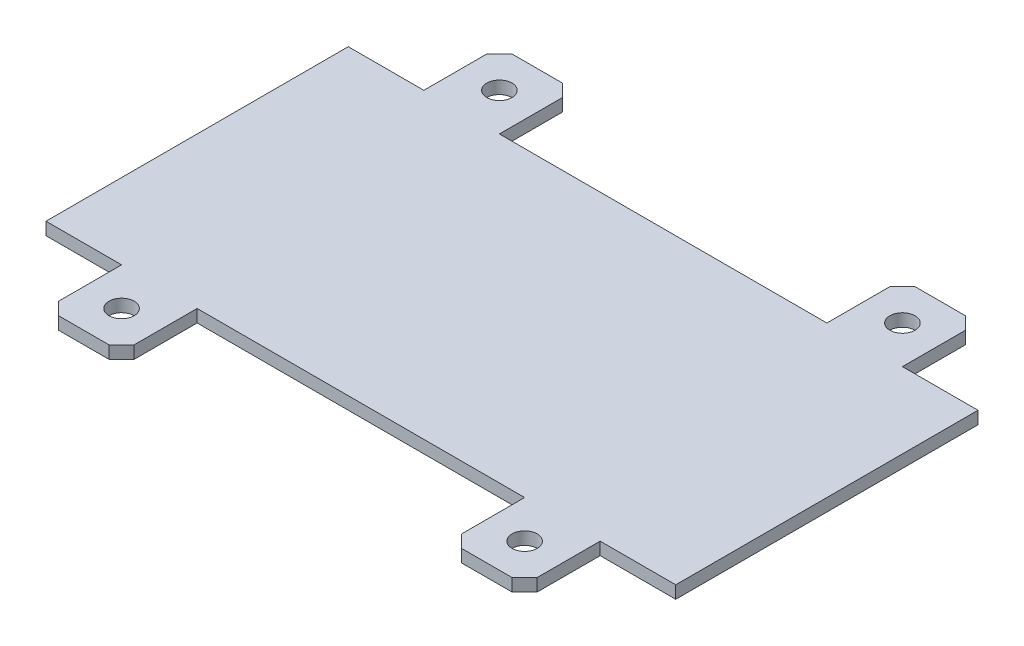
SolidWorks part; units mm, degrees
material "Сталь 3 ГОСТ 535-88"
ref_plane "Спереди" through (0, 0, 0) normal (0, 0, 1) x (1, 0, 0)
ref_plane "Сверху" through (0, 0, 0) normal (0, 1, 0) x (1, 0, 0)
ref_plane "Справа" through (0, 0, 0) normal (1, 0, 0) x (0, 0, -1)
sketch "Эскиз1" plane through (0, 0, 0) normal (0, 1, 0) x (1, 0, 0)
  line L1 (-125, 60) -> (125, 60)
  line L2 (-125, 60) -> (-125, -60)
  line L3 (-125, -60) -> (125, -60)
  line L4 (125, 60) -> (125, -60)
  line L5 (0, -60) -> (0, 60) construction
  line L6 (-125, 0) -> (125, 0) construction
  point P0 (0, 0)
  dimension "D1" = 120
  dimension "D2" = 250
extrude "Бобышка-Вытянуть1" add sketch "Эскиз1" along normal blind 5
sketch "Эскиз2" plane through (0, 0, 0) normal (0, 1, 0) x (1, 0, 0)
  line L0 (125, 60) -> (-125, 60) construction
  line L1 (-95, 60) -> (-65, 60)
  line L2 (-95, 60) -> (-95, 90)
  line L3 (-95, 90) -> (-65, 90)
  line L4 (-65, 60) -> (-65, 90)
  line L5 (-125, 60) -> (-125, -60) construction
  line L6 (-80, 90) -> (-80, 60) construction
  circle A0 centre (-80, 75) radius 5
  dimension "D4" = 10
  dimension "D1" = 30
  dimension "D2" = 30
  dimension "D3" = 30
extrude "Бобышка-Вытянуть2" add sketch "Эскиз2" along normal up to surface (5 mm away) separate body up to face at (0, 5, 0)
chamfer "Фаска1" distance 5 angle 45 2 edges at (-65, 2.5, -90) (-95, 2.5, -90)
mirror "Зеркальное отражение1" about plane through (0, 0, 0) normal (1, 0, 0) of bodies 112
mirror "Зеркальное отражение3" about plane through (0, 0, 0) normal (0, 0, 1) of bodies 112 113
combine bodies "Соединить1" operation type add bodies to combine 107 114 113 112 115
